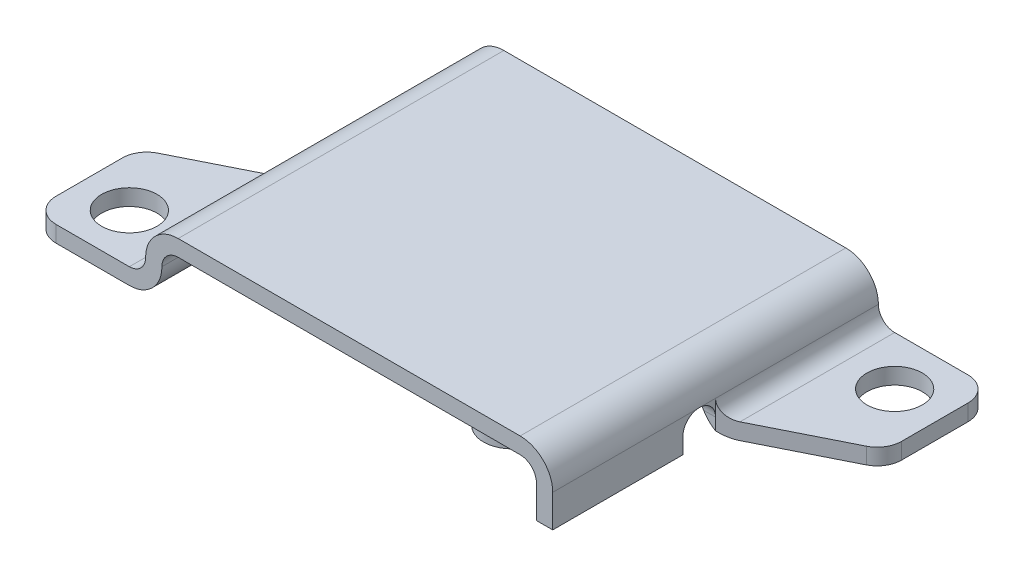
SolidWorks part; units mm, degrees
material "AISI Type 316L stainless steel"
ref_plane "Front" through (0, 0, 0) normal (0, 0, 1) x (1, 0, 0)
ref_plane "Top" through (0, 0, 0) normal (0, 1, 0) x (1, 0, 0)
ref_plane "Right" through (0, 0, 0) normal (1, 0, 0) x (0, 0, -1)
ref_axis "X-Axis" through (-80.9, 0, 0) along (1, 0, 0)
ref_axis "Y-Axis" through (0, -50, 0) along (0, 1, 0)
ref_axis "Z-Axis" through (0, 0, -80.9) along (0, 0, 1)
sketch "Sketch1" plane through (0, 0, 0) normal (0, 0, 1) x (1, 0, 0)
  line L0 (-12.5, -4) -> (-12.5, 0)
  line L1 (-12.5, 0) -> (12.5, 0)
  line L2 (12.5, 0) -> (12.5, -4)
  line L3 (12.5, -4) -> (11.5, -4)
  line L4 (11.5, -4) -> (11.5, -1)
  line L5 (11.5, -1) -> (-11.5, -1)
  line L6 (-11.5, -1) -> (-11.5, -4)
  line L7 (-11.5, -4) -> (-12.5, -4)
  line L8 (0, -1) -> (0, 0) construction
  dimension "D1" = 25
  dimension "D2" = 1
  dimension "D3" = 1
  dimension "D4" = 4
extrude "Boss-Extrude1" add sketch "Sketch1" along normal mid plane 20
sketch "Sketch3" plane through (12.5, 0, 0) normal (1, 0, 0) x (0, 0, -1)
  line L0 (-2, -3) -> (-2, -4)
  line L1 (-10, -4) -> (10, -4) construction
  line L2 (-2, -4) -> (0, -4)
  line L3 (0, -4) -> (0, -3)
  arc A0 (0, -3) -> (-2, -3) centre (-1, -3) ccw
  dimension "D2" = 2
  dimension "D1" = 1
extrude "Cut-Extrude1" cut sketch "Sketch3" against normal blind 1
pattern_circular "CirPattern1" count 2 over 180 about axis through (0, -50, 0) along (0, 1, 0) of "Cut-Extrude1"
sketch "Sketch4" plane through (0, -4, 0) normal (0, -1, 0) x (1, 0, 0)
  line L0 (12.5, -10) -> (19.5, -10)
  line L1 (19.5, -10) -> (19.5, -3.5)
  line L2 (19.5, -3.5) -> (12.5, 0)
  line L3 (12.5, 0) -> (12.5, -10)
  dimension "D1" = 7
  dimension "D2" = 6.5
extrude "Boss-Extrude2" add sketch "Sketch4" against normal blind 1
pattern_circular "CirPattern2" count 2 over 180 about axis through (0, -50, 0) along (0, 1, 0) of "Boss-Extrude2"
fillet "Fillet1" radius 1.5 4 edges at (-19.5, -3.5, 10) (-19.5, -3.5, 3.5) (19.5, -3.5, -10) (19.5, -3.5, -3.5)
fillet "Fillet2" radius 1 4 edges at (11.5, -1, 0) (-11.5, -1, 0)
fillet "Fillet3" radius 2 4 edges at (-12.5, 0, 0) (12.5, 0, 0) (11.5, -4, -5) (-11.5, -4, 5)
sketch "Sketch5" plane through (0, 0, 0) normal (0, 1, 0) x (1, 0, 0)
  line L1 (-16.5, -7) -> (16.5, -7) construction
  line L2 (-16.5, -7) -> (-16.5, 7) construction
  line L3 (-16.5, 7) -> (16.5, 7) construction
  line L4 (16.5, -7) -> (16.5, 7) construction
  line L5 (-16.5, -7) -> (16.5, 7) construction
  line L6 (-16.5, 7) -> (16.5, -7) construction
  circle A0 centre (16.5, 7) radius 1.7
  circle A1 centre (-16.5, -7) radius 1.7
  point P0 (0, 0)
  dimension "D3" = 3.4
  dimension "D1" = 33
  dimension "D2" = 14
extrude "Cut-Extrude2" cut sketch "Sketch5" against normal through all
sketch "Sketch6" plane through (0, -1, 0) normal (0, -1, 0) x (1, 0, 0)
  line L1 (-7.7, -7.7) -> (7.7, -7.7) construction
  line L2 (-7.7, -7.7) -> (-7.7, 7.7) construction
  line L3 (-7.7, 7.7) -> (7.7, 7.7) construction
  line L4 (7.7, -7.7) -> (7.7, 7.7) construction
  line L5 (-7.7, -7.7) -> (7.7, 7.7) construction
  line L6 (-7.7, 7.7) -> (7.7, -7.7) construction
  circle A0 centre (7.7, 7.7) radius 1.75
  circle A1 centre (-7.7, -7.7) radius 1.75
  point P0 (0, 0)
  dimension "D3" = 3.5
  dimension "D1" = 15.4
  dimension "D2" = 15.4
extrude "Boss-Extrude3" add sketch "Sketch6" along normal blind 1
